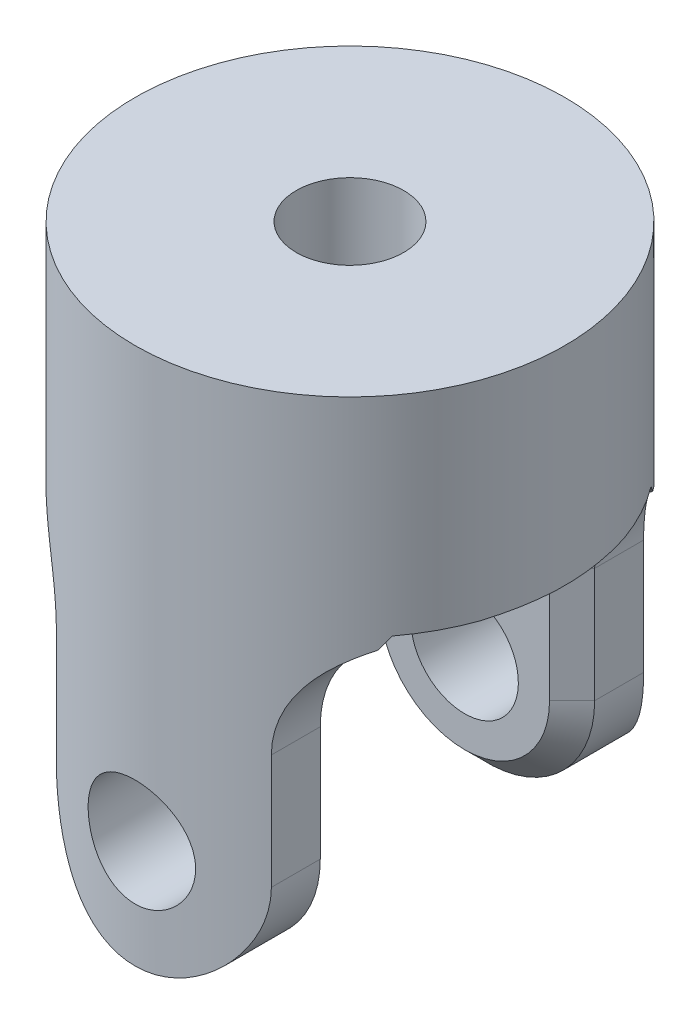
SolidWorks part; units mm, degrees
ref_plane "Front" through (0, 0, 0) normal (0, 0, 1) x (1, 0, 0)
ref_plane "Top" through (0, 0, 0) normal (0, 1, 0) x (-1, 0, 0)
ref_plane "Right" through (0, 0, 0) normal (1, 0, 0) x (0, 0, -1)
sketch "Sketch1" plane through (0, 0, 0) normal (0, 1, 0) x (-1, 0, 0)
  circle A0 centre (0, 0) radius 19.05
  dimension "D1" = 38.1
extrude "Base-Extrude" add sketch "Sketch1" along normal blind 47.625
sketch "Sketch2" plane through (0, 0, 0) normal (0, 0, 1) x (1, 0, 0)
  line L0 (0, 0) -> (0, 23.7435) construction
  line L1 (9.525, 9.525) -> (9.525, 19.685)
  line L2 (-9.525, 9.525) -> (-9.525, 19.685)
  line L3 (19.05, 29.21) -> (19.05, 0)
  line L4 (-19.05, 47.625) -> (-19.05, 0) construction
  line L5 (-19.05, 0) -> (-19.05, 29.21)
  line L6 (19.05, 0) -> (-19.05, 0) construction
  arc A0 (-9.525, 9.525) -> (9.525, 9.525) centre (0, 9.525) ccw
  arc A1 (9.525, 19.685) -> (19.05, 29.21) centre (19.05, 19.685) cw
  arc A2 (-9.525, 19.685) -> (-19.05, 29.21) centre (-19.05, 19.685) ccw
  dimension "D3" = 9.525
  dimension "D2" = 19.05
  dimension "D4" = 29.21
extrude "Cut-Extrude1" cut sketch "Sketch2" against normal through all and the other way through all flip side to cut
sketch "Sketch8" plane through (0, 0, 0) normal (1, 0, 0) x (0, 0, -1)
  line L0 (-19.05, 0) -> (19.05, 0) construction
  line L1 (-10.16, 0) -> (-10.16, 29.1452)
  line L2 (10.16, 29.1452) -> (-10.16, 29.1452)
  line L3 (10.16, 29.1452) -> (10.16, 0)
  line L4 (0, 0) -> (0, 14.3858) construction
  point P4 (0, 0)
  dimension "D1" = 29.1452
  dimension "D2" = 20.32
extrude "Cut-Extrude5" cut sketch "Sketch8" against normal through all and the other way through all flip side to cut
sketch "Sketch11" plane through (0, 0, 0) normal (0, 0, 1) x (1, 0, 0)
  circle A0 centre (0, 9.525) radius 4.7625
  dimension "D1" = 9.525
extrude "Cut-Extrude6" cut sketch "Sketch11" against normal through all and the other way through all
sketch "Sketch12" plane through (0, 47.625, 0) normal (0, 1, 0) x (-1, 0, 0)
  circle A0 centre (0, 0) radius 4.7625
  dimension "D1" = 9.525
extrude "Cut-Extrude7" cut sketch "Sketch12" against normal through all
ref_axis "Axis1" through (0, 97.625, 0) along (0, -1, 0)
chamfer "Chamfer1" distance 2 angle 45 10 edges at (-11.3465, 25.287, -10.16) (-9.525, 14.605, -10.16) (11.3465, 25.287, -10.16) (0, 0, -10.16) (9.525, 14.605, -10.16) (-11.3465, 25.287, 10.16) (-9.525, 14.605, 10.16) (0, 0, 10.16) (11.3465, 25.287, 10.16) (9.525, 14.605, 10.16)
